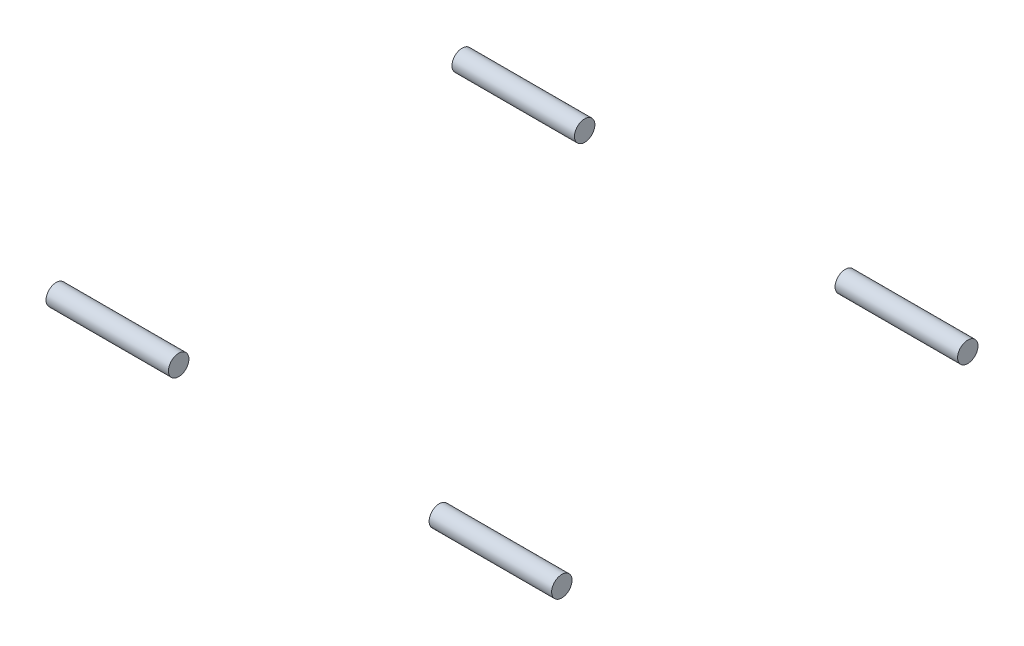
SolidWorks part; units mm, degrees
material "6061-T6 (SS)"
ref_plane "Front Plane" through (0, 0, 0) normal (0, 0, 1) x (1, 0, 0)
ref_plane "Top Plane" through (0, 0, 0) normal (0, 1, 0) x (1, 0, 0)
ref_plane "Right Plane" through (0, 0, 0) normal (1, 0, 0) x (0, 0, -1)
sketch "Sketch1" plane through (78.625, 0, 0) normal (-1, 0, 0) x (0, 0, 1)
  circle A0 centre (126.25, 0) radius 3.175
  circle A1 centre (0, 0) radius 3.175
  circle A2 centre (0, 0) radius 3.175 construction
  circle A3 centre (126.25, 0) radius 3.175 construction
extrude "Boss-Extrude1" add sketch "Sketch1" along normal blind 38.1
mirror "Mirror1" about plane through (0, 0, 0) normal (1, 0, 0) of bodies 101 102
